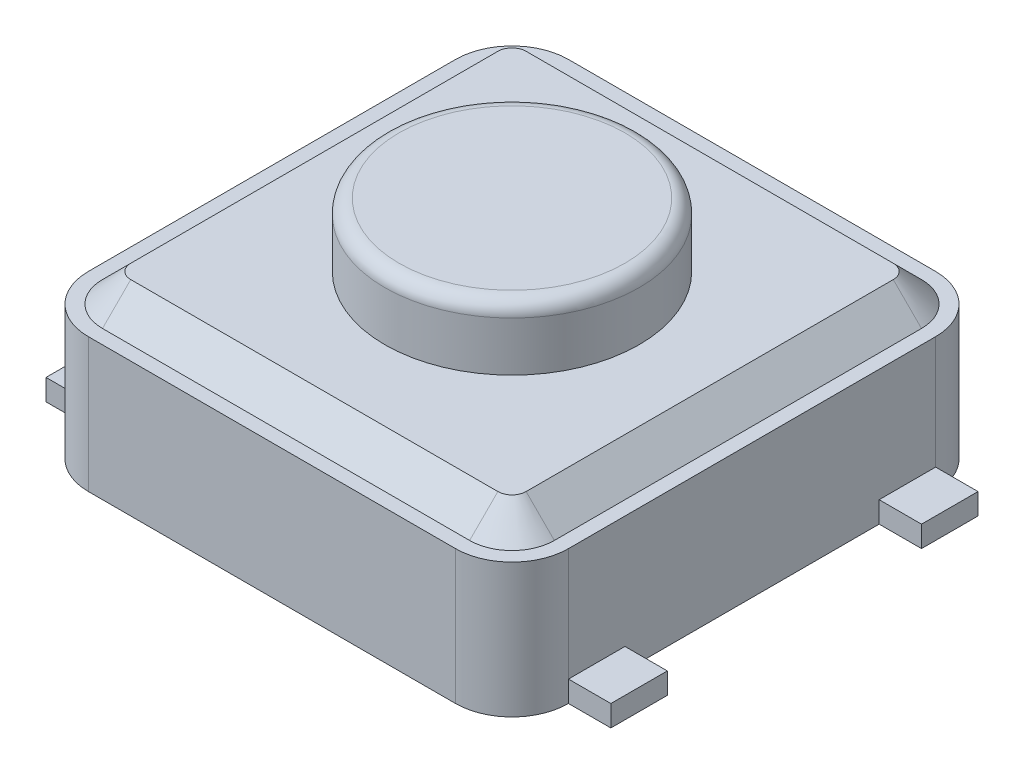
SolidWorks part; units mm, degrees
ref_plane "前视基准面" through (0, 0, 0) normal (0, 0, 1) x (1, 0, 0)
ref_plane "上视基准面" through (0, 0, 0) normal (0, 1, 0) x (1, 0, 0)
ref_plane "右视基准面" through (0, 0, 0) normal (1, 0, 0) x (0, 0, -1)
sketch "草图1" plane through (0, 0, 0) normal (0, 1, 0) x (1, 0, 0)
  line L1 (0, 0) -> (-1.7, 0)
  line L2 (0, 0) -> (0, 1.7)
  line L3 (0, 1.7) -> (-1.7, 1.7)
  line L4 (-1.7, 0) -> (-1.7, 1.7)
  dimension "D1" = 1.7
extrude "凸台-拉伸1" add sketch "草图1" along normal blind 1.15
sketch "草图2" plane through (0, 1.15, 0) normal (0, 1, 0) x (1, 0, 0)
  line L0 (-0.9, 0) -> (0, 0)
  line L1 (0, 0) -> (0, 0.9)
  arc A0 (0, 0.9) -> (-0.9, 0) centre (0, 0) ccw
  dimension "D1" = 0.9
extrude "凸台-拉伸2" add sketch "草图2" along normal blind 0.45
sketch "草图3" plane through (0, 0, 0) normal (0, -1, 0) x (1, 0, 0)
  line L0 (-1.7, -1.7) -> (-1.7, 0) construction
  line L1 (-1.7, -0.9) -> (-2, -0.9)
  line L2 (-1.7, -0.9) -> (-1.7, -1.3)
  line L3 (-1.7, -1.3) -> (-2, -1.3)
  line L4 (-2, -0.9) -> (-2, -1.3)
  line L5 (0, 0) -> (0, -1.7) construction
  line L6 (-1.7, 0) -> (0, 0) construction
  point P8 (-2, -1.1)
  dimension "D1" = 0.4
  dimension "D2" = 2
  dimension "D3" = 1.1
extrude "凸台-拉伸3" add sketch "草图3" against normal blind 0.15
sketch "草图4" plane through (0, 1.15, 0) normal (0, 1, 0) x (1, 0, 0)
  line L4 (0, 1.4) -> (-1.4, 1.4)
  line L5 (-1.4, 1.4) -> (-1.4, 0)
  line L6 (0, 1.4) -> (-1.4, 1.4)
  line L7 (-1.4, 1.4) -> (-1.4, 0)
  line L10 (0, 0.9) -> (0, 1.7)
  line L11 (0, 1.7) -> (-1.7, 1.7)
  line L12 (-1.7, 1.7) -> (-1.7, 0)
  line L13 (-1.7, 0) -> (-0.9, 0)
  line L14 (0, 1.4) -> (0, 1.7)
  line L15 (0, 1.7) -> (-1.7, 1.7)
  line L16 (-1.7, 1.7) -> (-1.7, 0)
  line L17 (-1.7, 0) -> (-1.4, 0)
  arc A1 (0, 0.9) -> (-0.9, 0) centre (0, 0) ccw
  dimension "D1" = 0.3
  dimension "D2" = 0
extrude "切除-拉伸1" cut sketch "草图4" against normal blind 0.2
fillet "圆角1" radius 0.4 1 edges at (-1.7, 0.475, -1.7)
fillet "圆角2" radius 0.1 1 edges at (-1.4, 1.05, -1.4)
chamfer "倒角1" distance 0.2 angle 45 3 edges at (-1.4, 0.95, -0.65) (-1.3707, 0.95, -1.3707) (-0.65, 0.95, -1.4)
fillet "圆角3" radius 0.1 1 edges at (-0.6364, 1.6, -0.6364)
mirror "镜向1" about plane through (0, 1.15, 0) normal (-1, 0, 0) of bodies 109
mirror "镜向2" about plane through (0, 1.15, 0) normal (0, 0, -1) of bodies 113
ref_plane "基准面1" through (0, 0, 0) normal (1, 0, 0) x (0, 0, -1)
